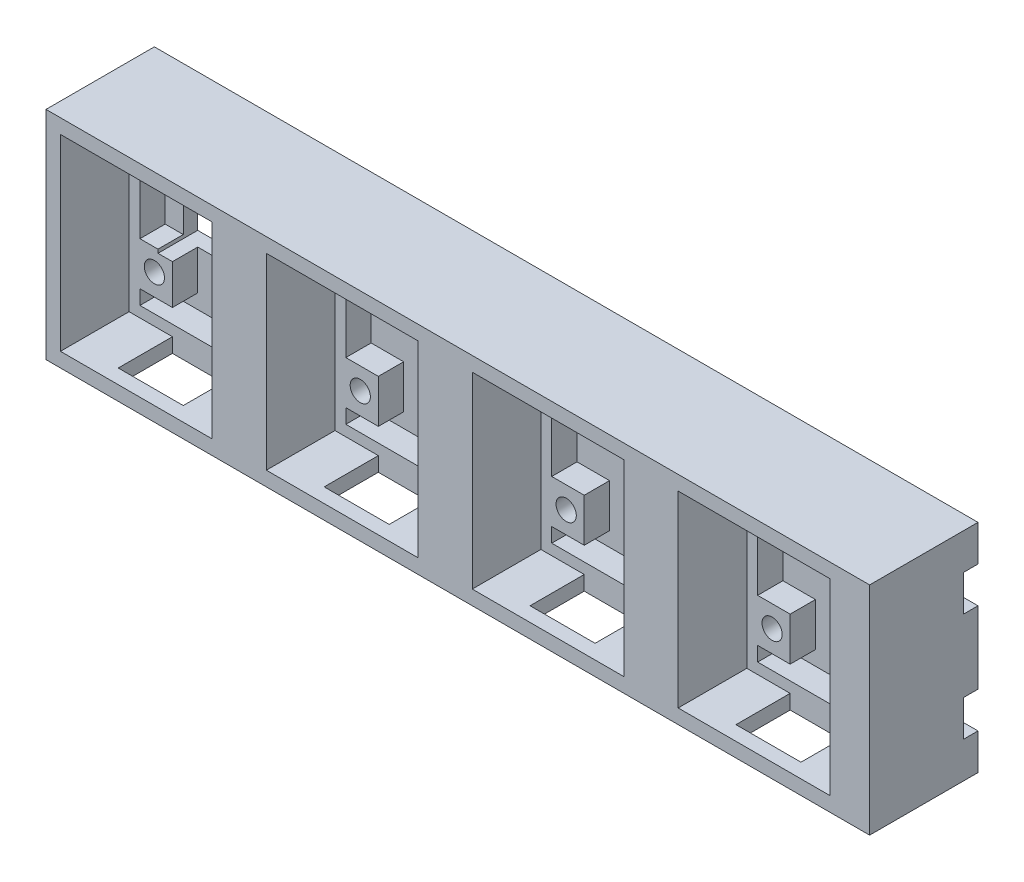
SolidWorks part; units mm, degrees
ref_plane "正面" through (0, 0, 0) normal (0, 0, 1) x (1, 0, 0)
ref_plane "平面" through (0, 0, 0) normal (0, 1, 0) x (1, 0, 0)
ref_plane "右側面" through (0, 0, 0) normal (1, 0, 0) x (0, 0, -1)
sketch "ｽｹｯﾁ1" plane through (0, 0, 0) normal (0, 0, 1) x (1, 0, 0)
  line L1 (-83.9031, 40.6786) -> (30.0969, 40.6786)
  line L2 (-83.9031, 40.6786) -> (-83.9031, 10.6786)
  line L3 (-83.9031, 10.6786) -> (30.0969, 10.6786)
  line L4 (30.0969, 40.6786) -> (30.0969, 10.6786)
  dimension "D1" = 30
extrude "ﾎﾞｽ - 押し出し1" add sketch "ｽｹｯﾁ1" along normal blind 15
sketch "ｽｹｯﾁ2" plane through (0, 0, 15) normal (0, 0, 1) x (1, 0, 0)
  line L0 (30.0969, 40.6786) -> (-83.9031, 40.6786) construction
  line L1 (-81.9031, 38.6786) -> (-60.9031, 38.6786)
  line L2 (-81.9031, 38.6786) -> (-81.9031, 12.6786)
  line L3 (-81.9031, 12.6786) -> (-60.9031, 12.6786)
  line L4 (-60.9031, 38.6786) -> (-60.9031, 12.6786)
  line L5 (-83.9031, 10.6786) -> (30.0969, 10.6786) construction
  line L7 (-83.9031, 40.6786) -> (-83.9031, 10.6786) construction
  line L8 (-58.9031, 40.6786) -> (-58.9031, 10.6786) construction
  line L9 (-55.4031, 40.6786) -> (-55.4031, 10.6786) construction
  line L10 (-30.4031, 40.6786) -> (-30.4031, 10.6786) construction
  line L11 (-26.9031, 40.6786) -> (-26.9031, 10.6786) construction
  line L12 (-1.9031, 40.6786) -> (-1.9031, 10.6786) construction
  line L13 (1.5969, 40.6786) -> (1.5969, 10.6786) construction
  line L14 (26.5969, 40.6786) -> (26.5969, 10.6786) construction
  line L16 (30.0969, 10.6786) -> (30.0969, 40.6786) construction
  line L18 (-53.4031, 38.6786) -> (-32.4031, 38.6786)
  line L19 (-53.4031, 38.6786) -> (-53.4031, 12.6786)
  line L20 (-53.4031, 12.6786) -> (-32.4031, 12.6786)
  line L21 (-32.4031, 38.6786) -> (-32.4031, 12.6786)
  line L22 (-24.9031, 38.6786) -> (-3.9031, 38.6786)
  line L23 (-24.9031, 38.6786) -> (-24.9031, 12.6786)
  line L24 (-24.9031, 12.6786) -> (-3.9031, 12.6786)
  line L25 (-3.9031, 38.6786) -> (-3.9031, 12.6786)
  line L26 (3.5969, 38.6786) -> (24.5969, 38.6786)
  line L27 (3.5969, 38.6786) -> (3.5969, 12.6786)
  line L28 (3.5969, 12.6786) -> (24.5969, 12.6786)
  line L29 (24.5969, 38.6786) -> (24.5969, 12.6786)
  dimension "D1" = 26
  dimension "D2" = 21
  dimension "D3" = 2
  dimension "D4" = 2
  dimension "D5" = 2
  dimension "D6" = 2
  dimension "D7" = 25
  dimension "D8" = 3.5
  dimension "D9" = 25
  dimension "D10" = 3.5
  dimension "D11" = 25
  dimension "D12" = 3.5
  dimension "D13" = 25
  dimension "D14" = 3.5
  dimension "D15" = 2
  dimension "D16" = 21
  dimension "D17" = 2
  dimension "D18" = 21
  dimension "D19" = 2
  dimension "D20" = 21
  dimension "D21" = 2
  dimension "D22" = 2
  dimension "D23" = 2
extrude "ｶｯﾄ - 押し出し1" cut sketch "ｽｹｯﾁ2" against normal blind 13
sketch "ｽｹｯﾁ3" plane through (0, 0, 2) normal (0, 0, 1) x (1, 0, 0)
  line L0 (-53.4031, 38.6786) -> (-53.4031, 12.6786) construction
  line L1 (-60.9031, 38.6786) -> (-81.9031, 38.6786)
  line L2 (-60.9031, 38.6786) -> (-60.9031, 12.6786)
  line L3 (-60.9031, 12.6786) -> (-81.9031, 12.6786)
  line L4 (-81.9031, 38.6786) -> (-81.9031, 12.6786)
  line L5 (-80.4031, 37.1786) -> (-62.4031, 37.1786)
  line L6 (-80.4031, 37.1786) -> (-80.4031, 14.1786)
  line L7 (-80.4031, 14.1786) -> (-62.4031, 14.1786)
  line L8 (-62.4031, 37.1786) -> (-62.4031, 14.1786)
  line L9 (-51.9031, 37.1786) -> (-33.9031, 37.1786)
  line L10 (-51.9031, 37.1786) -> (-51.9031, 14.1786)
  line L11 (-51.9031, 14.1786) -> (-33.9031, 14.1786)
  line L12 (-33.9031, 37.1786) -> (-33.9031, 14.1786)
  line L13 (-23.4031, 37.1786) -> (-5.4031, 37.1786)
  line L14 (-23.4031, 37.1786) -> (-23.4031, 14.1786)
  line L15 (-23.4031, 14.1786) -> (-5.4031, 14.1786)
  line L16 (-5.4031, 37.1786) -> (-5.4031, 14.1786)
  line L17 (5.0969, 37.1786) -> (23.0969, 37.1786)
  line L18 (5.0969, 37.1786) -> (5.0969, 14.1786)
  line L19 (5.0969, 14.1786) -> (23.0969, 14.1786)
  line L20 (23.0969, 37.1786) -> (23.0969, 14.1786)
  line L21 (-24.9031, 38.6786) -> (-24.9031, 12.6786) construction
  line L22 (3.5969, 38.6786) -> (3.5969, 12.6786) construction
  line L24 (-53.4031, 38.6786) -> (-32.4031, 38.6786)
  line L25 (-53.4031, 38.6786) -> (-53.4031, 12.6786)
  line L26 (-53.4031, 12.6786) -> (-32.4031, 12.6786)
  line L27 (-32.4031, 38.6786) -> (-32.4031, 12.6786)
  line L28 (-24.9031, 38.6786) -> (-3.9031, 38.6786)
  line L29 (-24.9031, 38.6786) -> (-24.9031, 12.6786)
  line L30 (-24.9031, 12.6786) -> (-3.9031, 12.6786)
  line L31 (-3.9031, 38.6786) -> (-3.9031, 12.6786)
  line L32 (3.5969, 38.6786) -> (24.5969, 38.6786)
  line L33 (3.5969, 38.6786) -> (3.5969, 12.6786)
  line L34 (3.5969, 12.6786) -> (24.5969, 12.6786)
  line L35 (24.5969, 38.6786) -> (24.5969, 12.6786)
  dimension "D1" = 1.5
  dimension "D2" = 1.5
  dimension "D3" = 1.5
  dimension "D4" = 1.5
  dimension "D5" = 1.5
  dimension "D6" = 1.5
  dimension "D7" = 1.5
  dimension "D8" = 26
  dimension "D9" = 21
  dimension "D10" = 26
  dimension "D11" = 21
  dimension "D12" = 26
  dimension "D13" = 21
extrude "ﾎﾞｽ - 押し出し2" add sketch "ｽｹｯﾁ3" along normal blind 3.5
sketch "ｽｹｯﾁ5" plane through (0, 0, 2) normal (0, 0, 1) x (1, 0, 0)
  line L0 (-62.4031, 14.1786) -> (-62.4031, 37.1786) construction
  line L1 (-62.4031, 22.1786) -> (-66.9031, 22.1786)
  line L2 (-62.4031, 22.1786) -> (-62.4031, 16.1786)
  line L3 (-62.4031, 16.1786) -> (-66.9031, 16.1786)
  line L4 (-66.9031, 22.1786) -> (-66.9031, 16.1786)
  line L5 (-51.9031, 37.1786) -> (-51.9031, 14.1786) construction
  line L6 (-81.9031, 12.6786) -> (-60.9031, 12.6786) construction
  line L7 (-80.4031, 37.1786) -> (-80.4031, 14.1786) construction
  line L8 (-80.4031, 22.1786) -> (-75.9031, 22.1786)
  line L9 (-80.4031, 22.1786) -> (-80.4031, 16.1786)
  line L10 (-80.4031, 16.1786) -> (-75.9031, 16.1786)
  line L11 (-75.9031, 22.1786) -> (-75.9031, 16.1786)
  line L12 (-51.9031, 22.1786) -> (-47.4031, 22.1786)
  line L13 (-51.9031, 22.1786) -> (-51.9031, 16.1786)
  line L14 (-51.9031, 16.1786) -> (-47.4031, 16.1786)
  line L15 (-47.4031, 22.1786) -> (-47.4031, 16.1786)
  line L16 (-33.9031, 14.1786) -> (-33.9031, 37.1786) construction
  line L17 (-33.9031, 22.1786) -> (-38.4031, 22.1786)
  line L18 (-33.9031, 22.1786) -> (-33.9031, 16.1786)
  line L19 (-33.9031, 16.1786) -> (-38.4031, 16.1786)
  line L20 (-38.4031, 22.1786) -> (-38.4031, 16.1786)
  line L21 (-23.4031, 37.1786) -> (-23.4031, 14.1786) construction
  line L22 (-23.4031, 22.1786) -> (-18.9031, 22.1786)
  line L23 (-23.4031, 22.1786) -> (-23.4031, 16.1786)
  line L24 (-23.4031, 16.1786) -> (-18.9031, 16.1786)
  line L25 (-18.9031, 22.1786) -> (-18.9031, 16.1786)
  line L26 (-5.4031, 14.1786) -> (-5.4031, 37.1786) construction
  line L27 (-5.4031, 22.1786) -> (-9.9031, 22.1786)
  line L28 (-5.4031, 22.1786) -> (-5.4031, 16.1786)
  line L29 (-5.4031, 16.1786) -> (-9.9031, 16.1786)
  line L30 (-9.9031, 22.1786) -> (-9.9031, 16.1786)
  line L31 (5.0969, 37.1786) -> (5.0969, 14.1786) construction
  line L32 (5.0969, 22.1786) -> (9.5969, 22.1786)
  line L33 (5.0969, 22.1786) -> (5.0969, 16.1786)
  line L34 (5.0969, 16.1786) -> (9.5969, 16.1786)
  line L35 (9.5969, 22.1786) -> (9.5969, 16.1786)
  line L36 (23.0969, 14.1786) -> (23.0969, 37.1786) construction
  line L37 (23.0969, 22.1786) -> (18.5969, 22.1786)
  line L38 (23.0969, 22.1786) -> (23.0969, 16.1786)
  line L39 (23.0969, 16.1786) -> (18.5969, 16.1786)
  line L40 (18.5969, 22.1786) -> (18.5969, 16.1786)
  point P10 (-66.9031, 19.1786)
  point P15 (-75.9031, 19.1786)
  dimension "D1" = 4.5
  dimension "D2" = 6
  dimension "D3" = 6.5
  dimension "D4" = 6.5
extrude "ﾎﾞｽ - 押し出し3" add sketch "ｽｹｯﾁ5" along normal blind 3.5
sketch "ｽｹｯﾁ6" plane through (0, 0, 5.5) normal (0, 0, 1) x (1, 0, 0)
  line L0 (-66.9031, 22.1786) -> (-66.9031, 16.1786) construction
  line L1 (-66.9031, 16.1786) -> (-62.4031, 16.1786) construction
  line L2 (-75.9031, 16.1786) -> (-75.9031, 22.1786) construction
  line L3 (-80.4031, 16.1786) -> (-75.9031, 16.1786) construction
  line L4 (-47.4031, 16.1786) -> (-47.4031, 22.1786) construction
  line L5 (-51.9031, 16.1786) -> (-47.4031, 16.1786) construction
  line L6 (-38.4031, 22.1786) -> (-38.4031, 16.1786) construction
  line L7 (-38.4031, 16.1786) -> (-33.9031, 16.1786) construction
  line L8 (-18.9031, 16.1786) -> (-18.9031, 22.1786) construction
  line L9 (-23.4031, 16.1786) -> (-18.9031, 16.1786) construction
  line L10 (-9.9031, 22.1786) -> (-9.9031, 16.1786) construction
  line L11 (-9.9031, 16.1786) -> (-5.4031, 16.1786) construction
  line L12 (9.5969, 16.1786) -> (9.5969, 22.1786) construction
  line L13 (5.0969, 16.1786) -> (9.5969, 16.1786) construction
  line L14 (18.5969, 22.1786) -> (18.5969, 16.1786) construction
  line L15 (18.5969, 16.1786) -> (23.0969, 16.1786) construction
  circle A0 centre (-64.4031, 19.1786) radius 1.4
  circle A1 centre (-78.4031, 19.1786) radius 1.4
  circle A2 centre (-49.9031, 19.1786) radius 1.4
  circle A3 centre (-35.9031, 19.1786) radius 1.4
  circle A4 centre (-21.4031, 19.1786) radius 1.4
  circle A5 centre (-7.4031, 19.1786) radius 1.4
  circle A6 centre (7.0969, 19.1786) radius 1.4
  circle A7 centre (21.0969, 19.1786) radius 1.4
  dimension "D1" = 2.8
  dimension "D4" = 2.5
  dimension "D5" = 3
  dimension "D6" = 2.5
  dimension "D2" = 2.5
  dimension "D3" = 3
  dimension "D7" = 3
  dimension "D8" = 2.5
  dimension "D9" = 3
  dimension "D10" = 2.5
  dimension "D11" = 3
  dimension "D12" = 2.5
  dimension "D13" = 3
  dimension "D14" = 2.5
  dimension "D15" = 3
  dimension "D16" = 2.5
  dimension "D17" = 3
extrude "ｶｯﾄ - 押し出し2" cut sketch "ｽｹｯﾁ6" against normal through all
sketch "ｽｹｯﾁ7" plane through (0, 12.6786, 0) normal (0, 1, 0) x (1, 0, 0)
  line L0 (-81.9031, -5.5) -> (-60.9031, -5.5) construction
  line L1 (-66.9031, -5.5) -> (-75.9031, -5.5)
  line L2 (-66.9031, -5.5) -> (-66.9031, -13)
  line L3 (-66.9031, -13) -> (-75.9031, -13)
  line L4 (-75.9031, -5.5) -> (-75.9031, -13)
  line L5 (-81.9031, -15) -> (-60.9031, -15) construction
  line L6 (-60.9031, -5.5) -> (-60.9031, -15) construction
  line L7 (-81.9031, -5.5) -> (-81.9031, -15) construction
  line L8 (-53.4031, -5.5) -> (-32.4031, -5.5) construction
  line L9 (-38.4031, -5.5) -> (-47.4031, -5.5)
  line L10 (-38.4031, -5.5) -> (-38.4031, -13)
  line L11 (-38.4031, -13) -> (-47.4031, -13)
  line L12 (-47.4031, -5.5) -> (-47.4031, -13)
  line L13 (-24.9031, -5.5) -> (-3.9031, -5.5) construction
  line L14 (-9.9031, -5.5) -> (-18.9031, -5.5)
  line L15 (-9.9031, -5.5) -> (-9.9031, -13)
  line L16 (-9.9031, -13) -> (-18.9031, -13)
  line L17 (-18.9031, -5.5) -> (-18.9031, -13)
  line L18 (3.5969, -5.5) -> (24.5969, -5.5) construction
  line L19 (18.5969, -5.5) -> (9.5969, -5.5)
  line L20 (18.5969, -5.5) -> (18.5969, -13)
  line L21 (18.5969, -13) -> (9.5969, -13)
  line L22 (9.5969, -5.5) -> (9.5969, -13)
  line L23 (-53.4031, -5.5) -> (-53.4031, -15) construction
  line L24 (-24.9031, -5.5) -> (-24.9031, -15) construction
  line L25 (3.5969, -5.5) -> (3.5969, -15) construction
  dimension "D1" = 2
  dimension "D2" = 6
  dimension "D3" = 6
  dimension "D4" = 7.5
  dimension "D5" = 9
  dimension "D6" = 7.5
  dimension "D7" = 9
  dimension "D8" = 7.5
  dimension "D9" = 9
  dimension "D10" = 6
  dimension "D11" = 6
  dimension "D12" = 6
extrude "ｶｯﾄ - 押し出し3" cut sketch "ｽｹｯﾁ7" against normal through all
sketch "ｽｹｯﾁ12" plane through (30.0969, 0, 0) normal (1, 0, 0) x (0, 0, -1)
  line L0 (0, 10.6786) -> (0, 40.6786) construction
  line L1 (0, 15.6786) -> (-2, 15.6786)
  line L2 (0, 15.6786) -> (0, 20.6786)
  line L3 (0, 20.6786) -> (-2, 20.6786)
  line L4 (-2, 15.6786) -> (-2, 20.6786)
  line L5 (-15, 10.6786) -> (0, 10.6786) construction
  line L6 (0, 30.6786) -> (-2, 30.6786)
  line L7 (0, 30.6786) -> (0, 35.6786)
  line L8 (0, 35.6786) -> (-2, 35.6786)
  line L9 (-2, 30.6786) -> (-2, 35.6786)
  line L10 (-15, 40.6786) -> (0, 40.6786) construction
  dimension "D1" = 5
  dimension "D2" = 5
  dimension "D3" = 5
  dimension "D4" = 5
  dimension "D5" = 2
  dimension "D6" = 2
extrude "ｶｯﾄ - 押し出し4" cut sketch "ｽｹｯﾁ12" against normal blind 3.5
sketch "ｽｹｯﾁ13" plane through (0, 0, 0) normal (0, 0, -1) x (-1, 0, 0)
  line L0 (73.9031, 25.6786) -> (73.9031, 10.6786) construction
  line L1 (83.9031, 10.6786) -> (-30.0969, 10.6786) construction
  line L2 (73.9031, 25.6786) -> (73.9031, 40.6786) construction
  line L3 (-30.0969, 40.6786) -> (83.9031, 40.6786) construction
  line L4 (83.9031, 40.6786) -> (83.9031, 10.6786) construction
  line L6 (77.9031, 21.6786) -> (69.9031, 21.6786)
  line L7 (77.9031, 21.6786) -> (77.9031, 29.6786)
  line L8 (77.9031, 29.6786) -> (69.9031, 29.6786)
  line L9 (69.9031, 21.6786) -> (69.9031, 29.6786)
  line L10 (77.9031, 21.6786) -> (69.9031, 29.6786) construction
  line L11 (77.9031, 29.6786) -> (69.9031, 21.6786) construction
  dimension "D1" = 10
  dimension "D2" = 8
  dimension "D3" = 8
extrude "ｶｯﾄ - 押し出し5" cut sketch "ｽｹｯﾁ13" against normal blind 10
